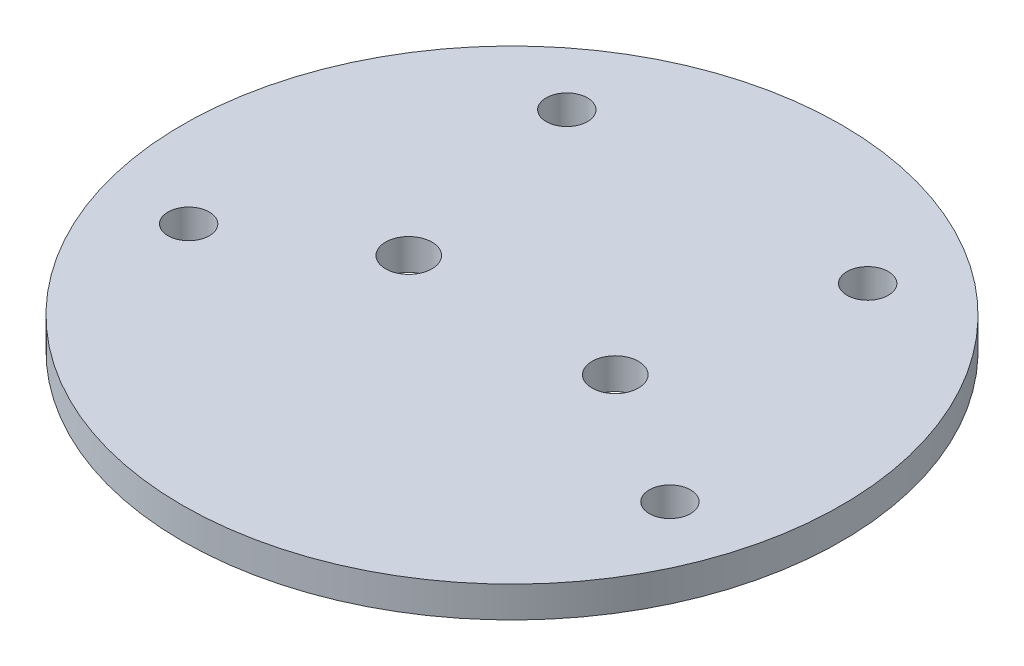
SolidWorks part; units mm, degrees
material "5052-H32"
ref_plane "Front Plane" through (0, 0, 0) normal (0, 0, 1) x (1, 0, 0)
ref_plane "Top Plane" through (0, 0, 0) normal (0, 1, 0) x (1, 0, 0)
ref_plane "Right Plane" through (0, 0, 0) normal (1, 0, 0) x (0, 0, -1)
sketch "Sketch1" plane through (0, 0, 0) normal (0, 1, 0) x (1, 0, 0)
  line L0 (0, 0) -> (-23.1297, 31.5565) construction
  line L1 (0, 0) -> (-41.7254, 0) construction
  line L2 (-37.0005, -12.7186) -> (0, 0) construction
  line L3 (0, -31.6103) -> (0, 47.1695) construction
  circle A0 centre (0, 0) radius 50.673
  circle A3 centre (-15.875, 0) radius 3.5687
  circle A4 centre (15.875, 0) radius 3.5687
  circle A5 centre (-37.0005, -12.7186) radius 3.175
  circle A8 centre (-23.1297, 31.5565) radius 3.175
  circle A9 centre (23.1297, 31.5565) radius 3.175
  circle A10 centre (37.0005, -12.7186) radius 3.175
  dimension "D1" = 101.346
  dimension "D2" = 6.35
  dimension "D3" = 6.35
  dimension "D5" = 15.875
  dimension "D6" = 15.875
  dimension "D4" = 39.1254
  dimension "D7" = 53.76
  dimension "D8" = 39.1254
  dimension "D9" = 18.97
extrude "Boss-Extrude1" add sketch "Sketch1" along normal blind 4.7752
equation "\"allrockets_tube_ID\"= 3.85in"
equation "\"allrockets_tube_OD\"= 4.024in"
equation "\"hole\"= 6.35mm"
equation "\"back_plate_width\"= 28mm"
equation "\"card_spacing\"= 20mm"
equation "\"card_number\"= 5"
equation "\"ToDi\"= 0.05mm"
equation "\"card_diameter\"= 85.86mm"
equation "\"overlap\"= 6.6mm"
equation "\"card_length\"= 68mm"
equation "\"rack_hole_tol\"= 0.60mm"
equation "\"rack_front_width\"= 11.63mm"
equation "\"hole_b_d\"= 39.12541885mm"
equation "\"hole_b_a\"= 18.9721389deg"
equation "\"hole_u_d\"= 39.12541885mm"
equation "\"hole_u_a\"= 53.76090642deg"
equation "\"card_h\"= 61.73mm"
equation "\"sphinx_av\"= 50.292mm"
equation "\"tb_spacing\"= 40mm"
equation "\"D2@Sketch1\"=\"hole\""
equation "\"D4@Sketch1\"=\"hole_u_d\""
equation "\"D7@Sketch1\"=\"hole_u_a\""
equation "\"D8@Sketch1\"=\"hole_b_d\""
equation "\"D9@Sketch1\"=\"hole_b_a\""
